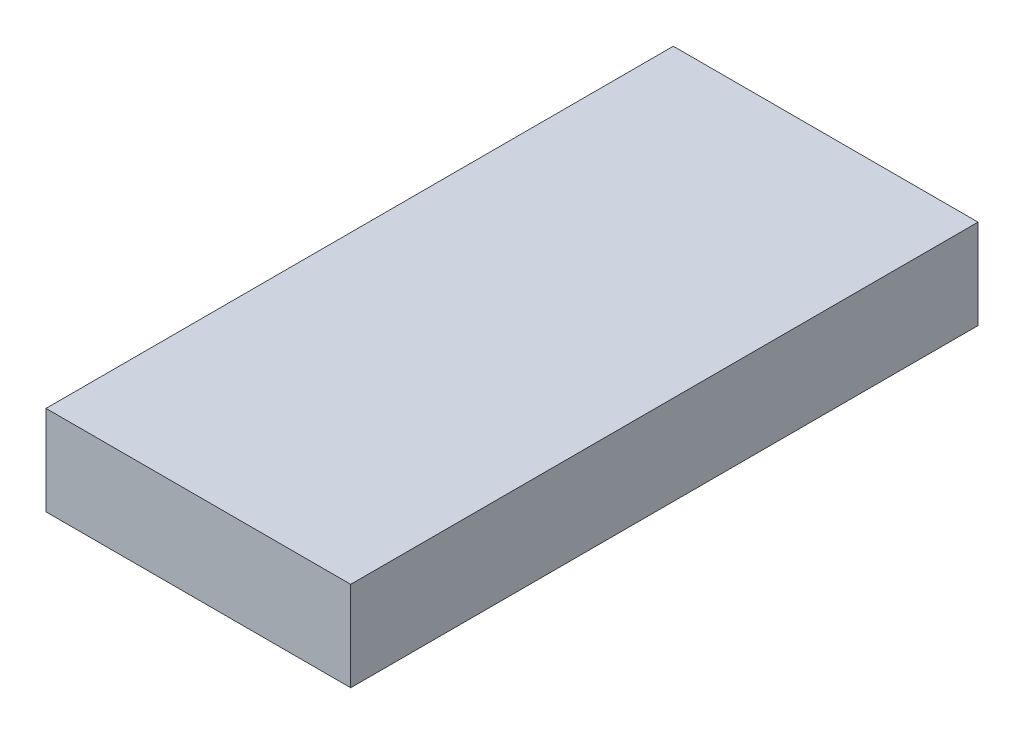
SolidWorks part; units mm, degrees
ref_plane "Front Plane" through (0, 0, 0) normal (0, 0, 1) x (1, 0, 0)
ref_plane "Top Plane" through (0, 0, 0) normal (0, 1, 0) x (1, 0, 0)
ref_plane "Right Plane" through (0, 0, 0) normal (1, 0, 0) x (0, 0, -1)
sketch "Sketch2" plane through (0, 0, 0) normal (0, 1, 0) x (1, 0, 0)
  line L0 (-279.9509, 0) -> (13717.5932, 0) construction
  line L1 (0, -279.9509) -> (0, 13717.5932) construction
  line L3 (-8.5, 17.5) -> (8.5, 17.5)
  line L4 (-8.5, 17.5) -> (-8.5, -17.5)
  line L5 (-8.5, -17.5) -> (8.5, -17.5)
  line L6 (8.5, 17.5) -> (8.5, -17.5)
  line L7 (-8.5, 17.5) -> (8.5, -17.5) construction
  line L8 (-8.5, -17.5) -> (8.5, 17.5) construction
  point P4 (0, 0)
  dimension "D1" = 17
  dimension "D2" = 35
extrude "Boss-Extrude1" add sketch "Sketch2" along normal blind 5
equation "\"Frame_Size\" = 220"
equation "\"Frame_Thickness\" = 6"
equation "\"Arm_Width\" = 30"
equation "\"Motor_Mount_Hole_Diameter\" = 8"
equation "\"Motor_Shaft_Diameter\" = 3"
equation "\"Screw_Nut_Diameter\" = 5"
equation "\"Screw_Diameter\" = 3"
equation "\"Screw_Shaft_Length\" = 10"
equation "\"Screw_Hole_Separation_C2C\" = 20"
equation "\"Solder_Board_Small_Screw_Hole_Separation\" = 37"
equation "\"Solder_Board_Small_Screw_Hole_Diameter\" = 3.3"
equation "\"Solder_Board_Small_Length\" = 45.72"
equation "\"Solder_Board_Small_Width\" = 33.02"
equation "\"Solder_Board_Small_Thickness\" = 1.6"
equation "\"ESC_Length\" = 35"
equation "\"ESC_Width\" = 17"
equation "\"ESC_Thickness\" = 5"
equation "\"D1@Sketch2\"=\"ESC_Width\""
equation "\"D2@Sketch2\"=\"ESC_Length\""
equation "\"D1@Boss-Extrude1\"=\"ESC_Thickness\""
